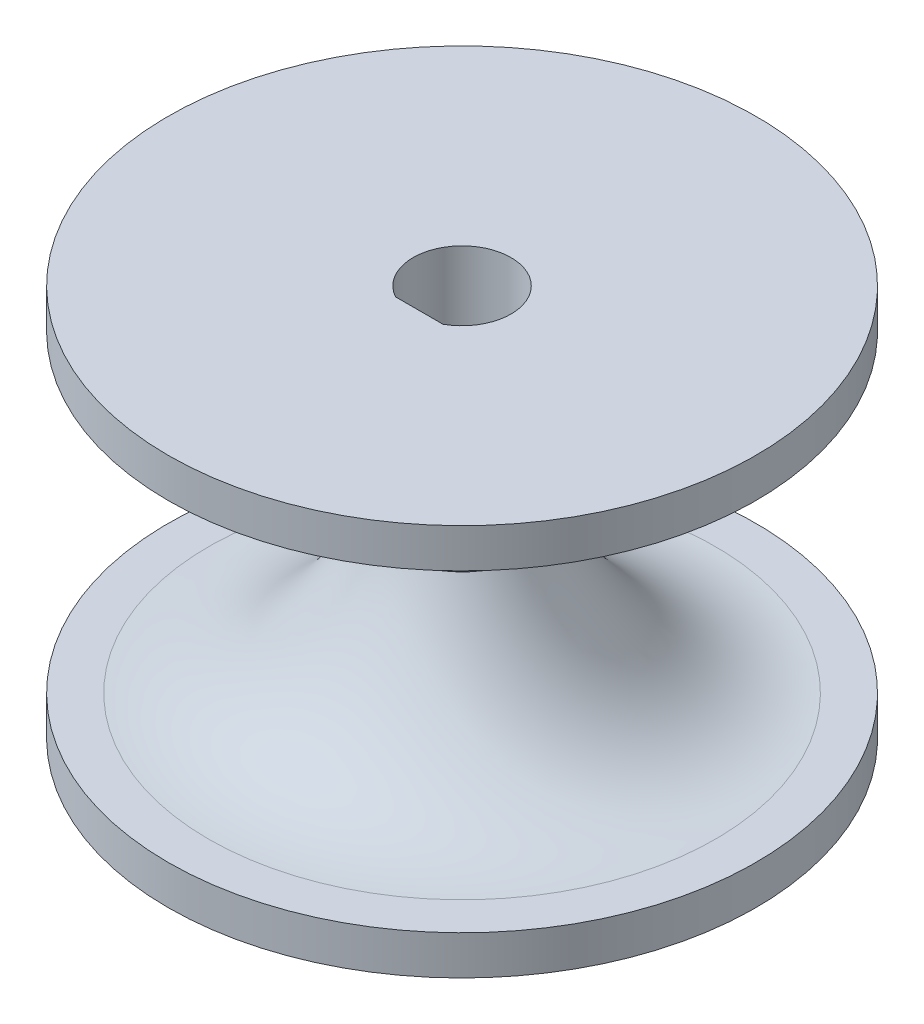
SolidWorks part; units mm, degrees
ref_plane "Front Plane" through (0, 0, 0) normal (0, 0, 1) x (1, 0, 0)
ref_plane "Top Plane" through (0, 0, 0) normal (0, 1, 0) x (1, 0, 0)
ref_plane "Right Plane" through (0, 0, 0) normal (1, 0, 0) x (0, 0, -1)
sketch "Sketch1" plane through (0, 0, 0) normal (0, 1, 0) x (1, 0, 0)
  circle A0 centre (0, 0) radius 24
extrude "Boss-Extrude1" add sketch "Sketch1" along normal blind 3.2
sketch "Sketch2" plane through (0, 3.2, 0) normal (0, 1, 0) x (1, 0, 0)
  circle A0 centre (0, 0) radius 6
extrude "Boss-Extrude2" add sketch "Sketch2" along normal blind 25.6
sketch "Sketch3" plane through (0, 28.8, 0) normal (0, 1, 0) x (1, 0, 0)
  circle A0 centre (0, 0) radius 24
extrude "Boss-Extrude3" add sketch "Sketch3" along normal blind 3.2 contours A0
sketch "Sketch4" plane through (0, 32, 0) normal (0, 1, 0) x (1, 0, 0)
  line L1 (0, -3.5) -> (-50000, -3.5) construction
  line L2 (-1.9365, -3.5) -> (1.9365, -3.5)
  arc A1 (1.9365, -3.5) -> (-1.9365, -3.5) centre (0, 0) ccw
extrude "Cut-Extrude1" cut sketch "Sketch4" against normal blind 10
ref_plane "Plane1" through (0, 0, 0) normal (0, 0, -1) x (-1, 0, 0)
sketch "Sketch5" plane through (0, 0, 0) normal (0, 0, -1) x (-1, 0, 0)
  line L2 (-6, 3.2) -> (-6, 16) construction
  line L3 (-6, 28.8) -> (-6, 3.2) construction
  line L4 (-24, 3.2) -> (-20.7, 3.2) construction
  line L5 (24, 3.2) -> (-24, 3.2) construction
  line L6 (-20.7, 3.2) -> (-20.7, 50003.2) construction
  line L7 (-20.7, 3.2) -> (-6, 3.2)
  line L8 (-6, 3.2) -> (-6, 16)
  spline S0 degree 2 poles (-6, 16) (-10.9911, 3.2989) (-20.7, 3.2) knots 0 0 0 0.984543 0.984543 0.984543
ref_plane "Plane2" through (0, 16, 0) normal (0, -1, 0) x (-1, 0, 0)
ref_axis "Axis1" through (0, 28.8, 0) along (0, -1, 0)
revolve "Revolve1" add sketch "Sketch5" angle 360 about axis through (0, 28.8, 0) along (0, -1, 0) region at (9.376, 6.794, 0)
mirror "Mirror1" about plane through (0, 16, 0) normal (0, -1, 0) of "Revolve1"
